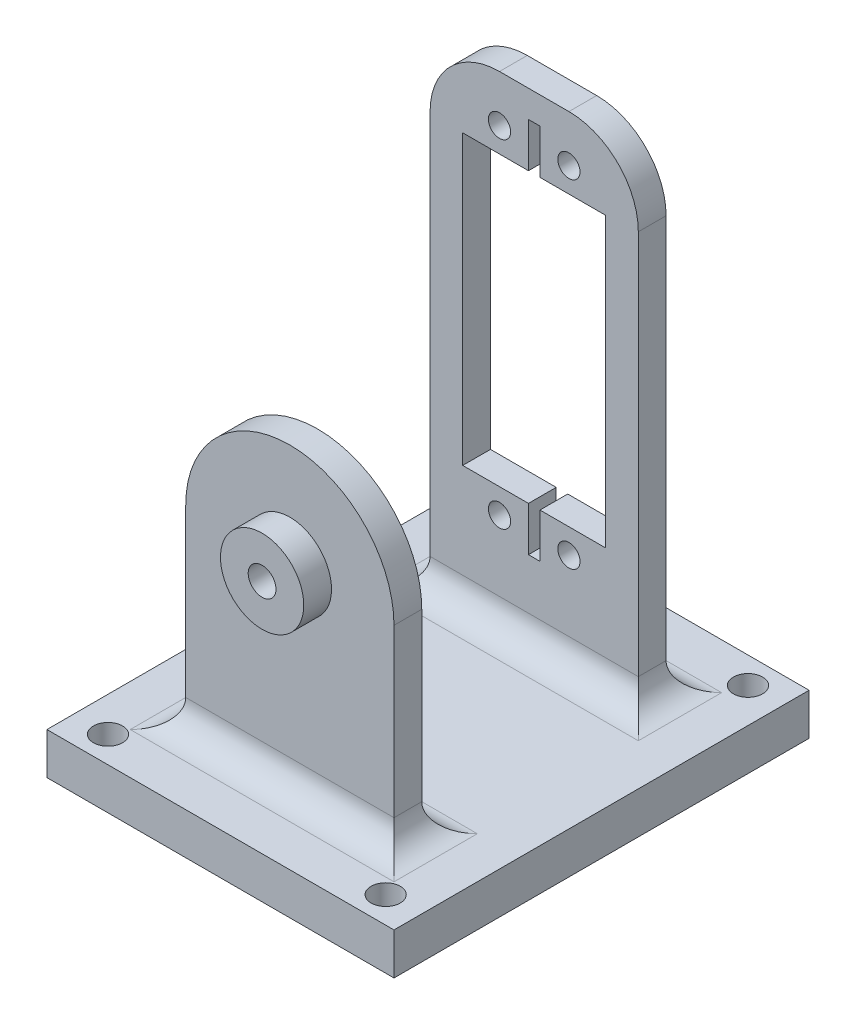
SolidWorks part; units mm, degrees
ref_plane "Front Plane" through (0, 0, 0) normal (0, 0, 1) x (1, 0, 0)
ref_plane "Top Plane" through (0, 0, 0) normal (0, 1, 0) x (1, 0, 0)
ref_plane "Right Plane" through (0, 0, 0) normal (1, 0, 0) x (0, 0, -1)
sketch "Sketch1" plane through (0, 0, 0) normal (0, 0, 1) x (1, 0, 0)
  line L0 (0, 0) -> (0, 53.2406) construction
  line L5 (-15, -28) -> (15, -28)
  line L6 (-15, -28) -> (-15, 31.5)
  line L7 (-5, 41.5) -> (5, 41.5)
  line L8 (15, -28) -> (15, 31.5)
  line L9 (0, 0) -> (15, 0) construction
  line L10 (-10.3, -10.3) -> (-0.83, -10.3)
  line L11 (-10.3, -10.3) -> (-10.3, 31.2)
  line L12 (-10.3, 31.2) -> (-0.83, 31.2)
  line L13 (10.3, -10.3) -> (10.3, 31.2)
  line L15 (-0.83, 31.2) -> (-0.83, 37.6)
  line L16 (-0.83, 37.6) -> (0.83, 37.6)
  line L17 (0.83, 31.2) -> (0.83, 37.6)
  line L18 (-10.3, 10.45) -> (10.3, 10.45) construction
  line L19 (-0.83, -10.3) -> (-0.83, -16.7)
  line L20 (-0.83, -16.7) -> (0.83, -16.7)
  line L21 (0.83, -10.3) -> (0.83, -16.7)
  line L22 (0.83, -10.3) -> (10.3, -10.3)
  line L23 (0.83, 31.2) -> (10.3, 31.2)
  arc A0 (5, 41.5) -> (15, 31.5) centre (5, 31.5) cw
  arc A1 (-15, 31.5) -> (-5, 41.5) centre (-5, 31.5) cw
  circle A2 centre (-5, 34.75) radius 1.6
  circle A3 centre (-5, -13.85) radius 1.6
  circle A4 centre (5, 34.75) radius 1.6
  circle A5 centre (5, -13.85) radius 1.6
  dimension "D4" = 10
  dimension "D10" = 3.2
  dimension "D13" = 3.2
  dimension "D1" = 30
  dimension "D2" = 41.5
  dimension "D3" = 28
  dimension "D5" = 20.6
  dimension "D6" = 31.2
  dimension "D7" = 10.3
  dimension "D8" = 5
  dimension "D9" = 34.75
  dimension "D11" = 5
  dimension "D12" = 13.85
  dimension "D14" = 37.6
  dimension "D15" = 1.66
extrude "Boss-Extrude1" add sketch "Sketch1" along normal blind 4
ref_plane "Plane1" through (0, 0, 39.2) normal (0, 0, 1) x (1, 0, 0)
sketch "Sketch2" plane through (0, 0, 39.2) normal (0, 0, 1) x (1, 0, 0)
  line L0 (0, 0) -> (0, 30.7043) construction
  line L1 (-15, -28) -> (15, -28)
  line L2 (-15, -28) -> (-15, 0)
  line L4 (15, -28) -> (15, 0)
  arc A0 (-15, 0) -> (15, 0) centre (0, 0) cw
  point P8 (0, 0)
  dimension "D3" = 15
  dimension "D1" = 30
  dimension "D2" = 28
extrude "Boss-Extrude2" add sketch "Sketch2" against normal blind 4 separate body
sketch "Sketch3" plane through (0, 0, 39.2) normal (0, 0, 1) x (1, 0, 0)
  circle A0 centre (0, 0) radius 6
  dimension "D1" = 12
extrude "Boss-Extrude3" add sketch "Sketch3" along normal blind 4
sketch "Sketch4" plane through (0, 0, 43.2) normal (0, 0, 1) x (1, 0, 0)
  circle A0 centre (0, 0) radius 2
  dimension "D1" = 4
extrude "Cut-Extrude1" cut sketch "Sketch4" against normal through all
ref_plane "Plane2" through (0, -28, 0) normal (0, 1, 0) x (1, 0, 0)
sketch "Sketch5" plane through (0, -28, 0) normal (0, 1, 0) x (1, 0, 0)
  line L0 (0, 0) -> (0, -51.9066) construction
  line L1 (-25, 10.6) -> (25, 10.6)
  line L2 (-25, 10.6) -> (-25, -49.2)
  line L3 (-25, -49.2) -> (25, -49.2)
  line L4 (25, 10.6) -> (25, -49.2)
  line L5 (-15, 0) -> (15, 0) construction
  line L7 (-16.5, -39.2) -> (16.5, -39.2) construction
  dimension "D2" = 10.6
  dimension "D1" = 50
  dimension "D3" = 10
  dimension "D4" = 59.8
extrude "Boss-Extrude4" add sketch "Sketch5" against normal blind 6
sketch "Sketch6" plane through (0, -34, 0) normal (0, -1, 0) x (1, 0, 0)
  line L0 (-25, 19.3) -> (25, 19.3) construction
  line L1 (-25, -10.6) -> (-25, 49.2) construction
  line L2 (25, 49.2) -> (25, -10.6) construction
  line L3 (0, 49.2) -> (0, -10.6) construction
  line L4 (-25, 49.2) -> (25, 49.2) construction
  line L5 (25, -10.6) -> (-25, -10.6) construction
  circle A0 centre (-20, 45.4) radius 2.1
  circle A1 centre (20, 45.4) radius 2.1
  circle A2 centre (20, -6.8) radius 2.1
  circle A3 centre (-20, -6.8) radius 2.1
  dimension "D1" = 4.2
  dimension "D2" = 20
  dimension "D3" = 45.4
extrude "Cut-Extrude2" cut sketch "Sketch6" against normal up to surface (6 mm away) up to face at (0, -28, 2)
fillet "Fillet1" radius 4 8 edges at (0, -28, 39.2) (-15, -28, 37.2) (15, -28, 37.2) (0, -28, 35.2) (15, -28, 2) (0, -28, 4) (-15, -28, 2) (0, -28, 0)
equation "\"L1\"= 120mm'Upper arm"
equation "\"L3\"= 75mm'Wrist→TCP"
equation "\"h0\"= 75mm'Shoulder height"
equation "\"t_link\"= 3mm'Link plate thickness"
equation "\"t_bracket\"= 4mm'Bracket thickness"
equation "\"d_pin\"= 4mm'Pin diameter (M4)"
equation "\"c_fit\"= 0.2mm'Nominal clearance - measured PLA 2026-10-01"
equation "\"L2\"= 120mm'Forearm"
equation "\"c_fit_pivot\"= \"c_fit\" + 0.05mm'Gripper pivot clearance - chosen 0.25 mm 2026-10-01"
equation "\"d_pin_gripper\"= 3mm'Gripper pivot diameter"
equation "\"w_link\"= 20mm'Link plate depth (bending direction)"
equation "\"w_gap\"= 20mm'Twin-plate gap - provisional, set by elbow servo mount"
equation "\"d_boss\"= 13mm'MG996R output boss dia - from downloaded model, verify with calipers"
equation "\"c_boss\"= 1mm'Radial clearance around servo boss"
equation "\"d_servo_hole\"= \"d_boss\" + 2 * \"c_boss\"'Plate clearance hole for servo boss (15 mm)"
equation "\"t_rim\"= 9.5mm'Min material around servo hole (M3 hole + 3 mm webs each side)"
equation "\"w_link_end\"= \"d_servo_hole\" + 2 * \"t_rim\"'Link plate end width at servo end (34 mm)"
equation "\"d_hole_m3\"= \"d_pin_gripper\" + \"c_fit\"'M3 bolt clearance hole (spacer and adapter bolts)"
equation "\"d_hole_pivot\"= \"d_pin\" + \"c_fit_pivot\"'M4 pivot hole where the pin rotates (4.25 mm)"
equation "\"d_horn\"= 20mm'Horn disc diameter (circular horn) - from MG996R model"
equation "\"t_horn\"= 2.3mm'Horn disc thickness"
equation "\"g_horn\"= 2.2mm'Gap from horn disc to plate 2 inner face - from MockShoulder"
equation "\"d_horn_pocket\"= \"d_horn\" + \"c_fit\"'Adapter pocket for horn disc (20.2 mm)"
equation "\"h_horn_pocket\"= \"g_horn\" + \"t_horn\"'Pocket depth from adapter plate-2 face (4.5 mm)"
equation "\"d_horn_screw_cb\"= 8.5mm'Recess for horn centre-screw head (head is 7.5 mm)"
equation "\"h_horn_screw_cb\"= 2.6mm'Recess depth (head is 2.35 mm tall)"
equation "\"d_adapter\"= 26mm'Horn adapter outer diameter"
equation "\"h_adapter\"= \"w_gap\"'Adapter length, fills the plate gap"
equation "\"t_adapter_floor\"= 2mm'Floor under horn disc that the horn screws pass through"
equation "\"d_horn_screw_hole\"= 2.2mm'Clearance for M2 self-tapper through the floor"
equation "\"r_horn_screw\"= 7mm'Horn screw hole radius (14 mm square pattern)"
equation "\"d_access\"= 4mm'Access bore for the M2 screws from the plate-1 side"
equation "\"d_insert_m3\"= 4.2mm'Hole for M3 heat-set insert - check the insert maker spec"
equation "\"h_insert_m3\"= 6mm'Insert hole depth"
equation "\"x_adapter_bolt\"= 6mm'Adapter bolt offset from pin, along the arm toward its middle"
equation "\"y_adapter_bolt\"= 5mm'Adapter bolt offset from pin, across the arm (+/-)"
equation "\"d_csk_m3\"= 6.4mm'Countersink diameter in plate 1 for M3 flat head (90 deg)"
equation "\"h_pin_bore\"= 10mm'M4 pin engagement depth in the adapter"
equation "\"c_win\"= 0.3mm'Servo window clearance per side in bracket wall A - starting value, tune after a test print"
equation "\"l_servo\"= 40.9mm'MG996R case length without ears - from the model"
equation "\"w_servo\"= 20mm'MG996R case width - from the model"
equation "\"r_servo_short\"= 10mm'Shaft axis to the short end of the case - from the model"
equation "\"r_servo_long\"= \"l_servo\" - \"r_servo_short\"'Shaft axis to the long end of the case (30.9 mm)"
equation "\"l_ear_holes\"= 48.6mm'MG996R ear hole (keyhole slot) spacing along the case - from the model"
equation "\"w_ear_holes\"= 10mm'MG996R ear hole spacing across the case - from the model"
equation "\"a_ear\"= 8.2mm'Servo ear seating face to plate-2 outer face - from MockShoulder (ear face incl. 0.2 edge round)"
equation "\"l_window\"= \"l_servo\" + 2 * \"c_win\"'Wall A window length (41.5 mm)"
equation "\"w_window\"= \"w_servo\" + 2 * \"c_win\"'Wall A window width (20.6 mm)"
equation "\"g_wall_a\"= \"a_ear\" - \"t_bracket\"'Gap behind wall A to plate 2 (4.4 mm) - ear screw heads sit here"
equation "\"g_wall_b\"= 1mm'Plate 1 outer face to wall B - thrust washer"
equation "\"d_axis_turret\"= 34mm'Shoulder axis to turret mounting face - PLACEHOLDER until the turret is designed"
equation "\"t_foot\"= 6mm'Bracket foot thickness"
equation "\"h_wall_top\"= 41.5mm'Wall A top above the shoulder axis (long-end ear holes + 4 mm)"
equation "\"w_wall\"= 30mm'Bracket wall A and B width"
equation "\"w_foot\"= 50mm'Bracket foot width across the walls"
equation "\"t_boss_b\"= 4mm'Extra thickness of the pin boss on the outside of wall B"
equation "\"d_boss_b\"= 12mm'Pin boss diameter on wall B"
equation "\"D1@Sketch1\"=\"w_wall\""
equation "\"D2@Sketch1\"=\"h_wall_top\""
equation "\"D3@Sketch1\"=\"d_axis_turret\" - \"t_foot\""
equation "\"D5@Sketch1\"=\"w_window\""
equation "\"D6@Sketch1\"=\"r_servo_long\" + \"c_win\""
equation "\"D7@Sketch1\"=\"r_servo_short\" + \"c_win\""
equation "\"D8@Sketch1\"=\"w_ear_holes\"/2"
equation "\"D9@Sketch1\"=\"l_ear_holes\"/2 + \"l_servo\"/2 - \"r_servo_short\""
equation "\"D10@Sketch1\"=\"d_hole_m3\""
equation "\"D11@Sketch1\"=\"w_ear_holes\"/2"
equation "\"D12@Sketch1\"=\"l_ear_holes\"/2 - (\"l_servo\"/2 - \"r_servo_short\")"
equation "\"D13@Sketch1\"=\"d_hole_m3\""
equation "\"D1@Boss-Extrude1\"=\"t_bracket\""
equation "\"D1@Sketch3\"=\"d_boss_b\""
equation "\"D1@Boss-Extrude3\"=\"t_boss_b\""
equation "\"D1@Sketch4\"=\"d_pin\""
equation "\"D1@Sketch5\"=\"w_foot\""
equation "\"D1@Boss-Extrude4\"=\"t_foot\""
equation "\"D1@Sketch6\"=\"d_insert_m3\""
